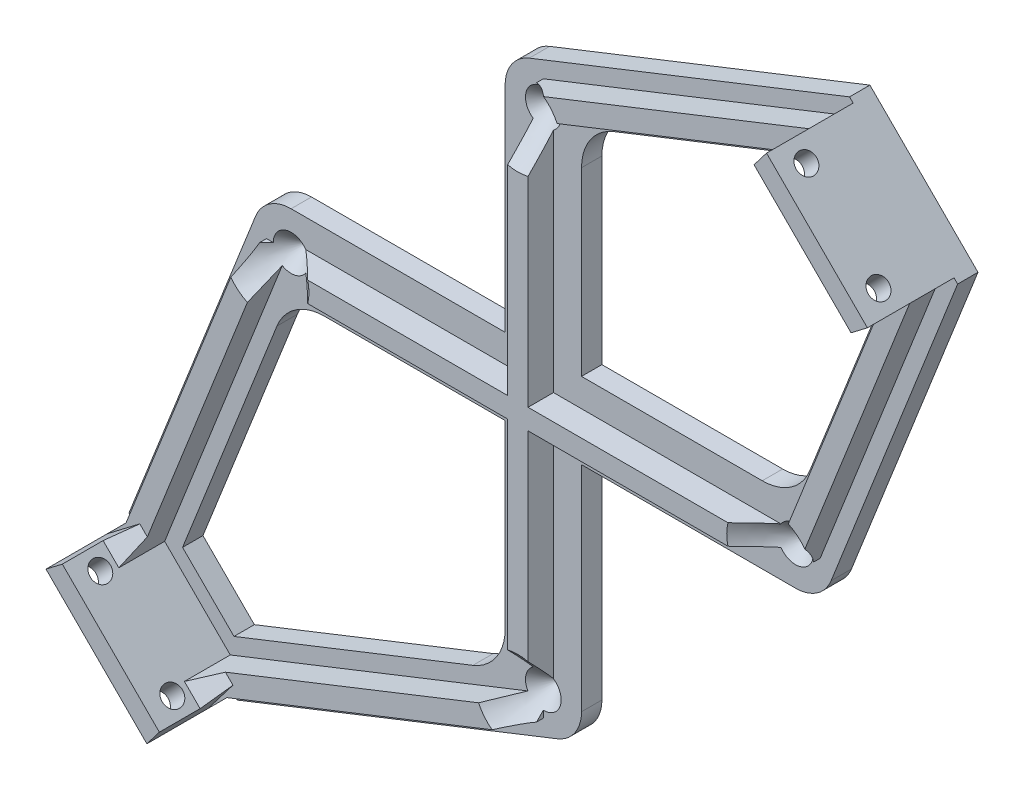
SolidWorks part; units mm, degrees
ref_plane "Top Plane" through (0, 0, 0) normal (0, 0, 1) x (1, 0, 0)
ref_plane "Right Plane" through (0, 0, 0) normal (0, 1, 0) x (1, 0, 0)
ref_plane "Front Plane" through (0, 0, 0) normal (1, 0, 0) x (0, 0, -1)
sketch "Sketch2" plane through (0, 0, -76.4826) normal (0, 0, -1) x (-1, 0, 0)
  line L0 (0, 0) -> (0, 99) construction
  line L1 (-7.5, 0) -> (-7.5, 42)
  line L2 (7.5, 0) -> (7.5, 42)
  line L3 (-49.5, 49.5) -> (49.5, 49.5) construction
  line L4 (-49.5, 57) -> (-7.5, 57)
  line L5 (-49.5, 42) -> (-7.5, 42)
  line L6 (-7.5, 49.5) -> (-7.5, 99)
  line L7 (-7.5, 42) -> (-7.5, 49.5) construction
  line L8 (7.5, 42) -> (49.5, 42)
  line L9 (-7.5, 42) -> (0, 42) construction
  line L10 (0, 42) -> (7.5, 42) construction
  line L11 (7.5, 57) -> (7.5, 99)
  line L12 (7.5, 49.5) -> (7.5, 57) construction
  line L13 (7.5, 42) -> (7.5, 49.5) construction
  line L14 (7.5, 57) -> (49.5, 57)
  line L15 (0, 57) -> (7.5, 57) construction
  line L16 (-7.5, 57) -> (0, 57) construction
  circle A0 centre (0, 0) radius 0.5
  circle A1 centre (-49.5, 49.5) radius 0.5
  circle A2 centre (0, 99) radius 0.5
  circle A3 centre (49.5, 49.5) radius 0.5
  arc A8 (-7.5, 0) -> (7.5, 0) centre (0, 0) ccw
  arc A9 (7.5, 99) -> (-7.5, 99) centre (0, 99) ccw
  arc A10 (-49.5, 57) -> (-49.5, 42) centre (-49.5, 49.5) ccw
  arc A11 (49.5, 42) -> (49.5, 57) centre (49.5, 49.5) ccw
  circle M17 centre (0, 0) radius 1.5
  circle M18 centre (0, 0) radius 3.95
  dimension "D2" = 1
  dimension "D1" = 15
extrude "Boss-Extrude1" add sketch "Sketch2" along normal blind 4 contours L8 A11 L14 L11 A9 L6 L4 A10 L5 L1 A8 L2 A1 A2 A3 M18 | A0 M17 | M18 M17 region at (0, 50.2835, -76.4826) region at (1.4576, 0, -76.4826) region at (3.8383, 0, -76.4826)
chamfer "Chamfer1" distance 3 angle 45 4 edges at (-0.5, 99, -76.4826) (-50, 49.5, -76.4826) (49, 49.5, -76.4826) (-0.5, 0, -76.4826)
sketch "Sketch3" plane through (0, 0, -80.4826) normal (0, 0, -1) x (-1, 0, 0)
  line L0 (56.4751, 52.2565) -> (81.3173, -10.6041)
  line L1 (81.3173, -10.6041) -> (70.7107, -21.2107)
  line L2 (63.3634, -13.8634) -> (71.4178, -21.9178) construction
  line L3 (70.7107, -21.2107) -> (65.7609, -16.2609)
  line L4 (54.3855, -4.8855) -> (62.6563, -13.1563) construction
  line L5 (65.7609, -16.2609) -> (70.8063, -11.2155)
  line L7 (61.1647, -30.7566) -> (80.2566, -11.6647) construction
  line L8 (70.8063, -11.2155) -> (49.7738, 42.005)
  line L10 (49.7738, 42.005) -> (56.4751, 52.2565)
  arc A0 (49.5, 42) -> (49.5, 57) centre (49.5, 49.5) ccw construction
  dimension "D1" = 15
  dimension "D2" = 10
  dimension "D3" = 7
extrude "Boss-Extrude2" add sketch "Sketch3" against normal up to surface (4 mm away) up to face at (-3.5, 99, -76.4826)
fillet "Fillet1" radius 10 1 edges at (-49.7738, 42.005, -78.4826)
sketch "Sketch5" plane through (0, 0, -76.4826) normal (0, 0, 1) x (1, 0, 0)
  line L0 (0, 49.5) -> (-2, 51.5)
  line L1 (-2, 51.5) -> (-46.6277, 51.5)
  line L4 (-54.3387, 49.5) -> (-76.9078, -7.6088)
  line L5 (0, 49.5) -> (-2, 47.5)
  line L6 (-2, 47.5) -> (-46.6277, 47.5)
  line L9 (-51.2382, 46.4621) -> (-74.3201, -11.9444)
  line L10 (-74.3201, -11.9444) -> (-67.8823, -18.3823)
  line L11 (-70.7107, -21.2107) -> (-65.7609, -16.2609) construction
  line L12 (-67.8823, -18.3823) -> (-70.7107, -21.2107)
  line L13 (-70.7107, -21.2107) -> (-79.0052, -12.9161)
  line L14 (-81.3173, -10.6041) -> (-70.7107, -21.2107) construction
  line L15 (-62.7792, 17.2589) -> (-59.9891, 16.1563) construction
  line L16 (-70.8063, -11.2155) -> (-52.2753, 35.6754) construction
  line L17 (-66.1061, 19.7236) -> (-68.8962, 20.8262) construction
  line L18 (-56.4751, 52.2565) -> (-81.3173, -10.6041) construction
  line L19 (-76.9078, -7.6088) -> (-79.0052, -12.9161) construction
  line L20 (-49.5, 49.5) -> (49.5, 49.5) construction
  line L21 (-54.3387, 49.5) -> (-49.5, 49.5) construction
  line L22 (-54.3387, 49.5) -> (-53, 49.5)
  line L23 (-79.0052, -12.9161) -> (-80.6102, -11.3112)
  line L24 (-24.3139, 51.5) -> (-24.3139, 47.5) construction
  line L25 (-80.6102, -11.3112) -> (-76.9078, -7.6088)
  arc A0 (-53, 49.5) -> (-51.2382, 46.4621) centre (-49.5, 49.5) ccw
  circle A1 centre (-49.5, 49.5) radius 3.5 construction
  arc A2 (-46.6277, 47.5) -> (-46.6277, 51.5) centre (-49.5, 49.5) ccw
  point P4 (-24.3139, 49.5)
  dimension "D1" = 4
  dimension "D2" = 4
  dimension "D3" = 4
  dimension "D4" = 14
extrude "Boss-Extrude4" add sketch "Sketch5" along normal blind 5
chamfer "Chamfer2" distance 5 angle 45 2 edges at (-46, 49.5, -71.4826) (-52.5277, 47.7441, -71.4826)
mirror "Mirror2" about plane through (-70.7107, -21.2107, 3.47) normal (0.7071, -0.7071, 0) of bodies 105
sketch "Sketch6" plane through (0, 0, -71.4826) normal (0, 0, 1) x (1, 0, 0)
  line L0 (-80.6102, -11.3112) -> (-60.8112, -31.1102)
  line L1 (-60.8112, -31.1102) -> (-58.3616, -27.9029)
  line L2 (-5.0525, -6.8354) -> (-57.1088, -27.4078) construction
  line L3 (-58.3616, -27.9029) -> (-77.4029, -8.8616)
  line L4 (-56.3354, 44.4475) -> (-76.9078, -7.6088) construction
  line L5 (-77.4029, -8.8616) -> (-80.6102, -11.3112)
  line L6 (-61.4444, -24.8201) -> (-74.3201, -11.9444) construction
  line L7 (-57.1088, -27.4078) -> (-60.8112, -31.1102) construction
extrude "Boss-Extrude5" add sketch "Sketch6" along normal blind 12
chamfer "Chamfer3" distance 4 angle 45 2 edges at (-59.903, -26.3615, -71.4826) (-75.8615, -10.403, -71.4826)
sketch "Sketch7" plane through (-43.1323, -43.1323, 0) normal (0.7071, 0.7071, 0) x (0, 0, -1)
  line L0 (64.4826, 45.0018) -> (64.4826, 25.0018) construction
  line L2 (59.4826, 21.5376) -> (59.4826, 48.466) construction
  line L3 (59.4826, 35.0018) -> (64.4826, 35.0018) construction
  circle A0 centre (64.4826, 45.0018) radius 2
  circle A1 centre (64.4826, 25.0018) radius 2
  dimension "D2" = 4
  dimension "D3" = 5
  dimension "D1" = 20
extrude "Cut-Extrude1" cut sketch "Sketch7" against normal through all
mirror "Mirror3" about plane through (0, 49.5, -71.4826) normal (-0.7071, -0.7071, 0) of bodies 110 107
